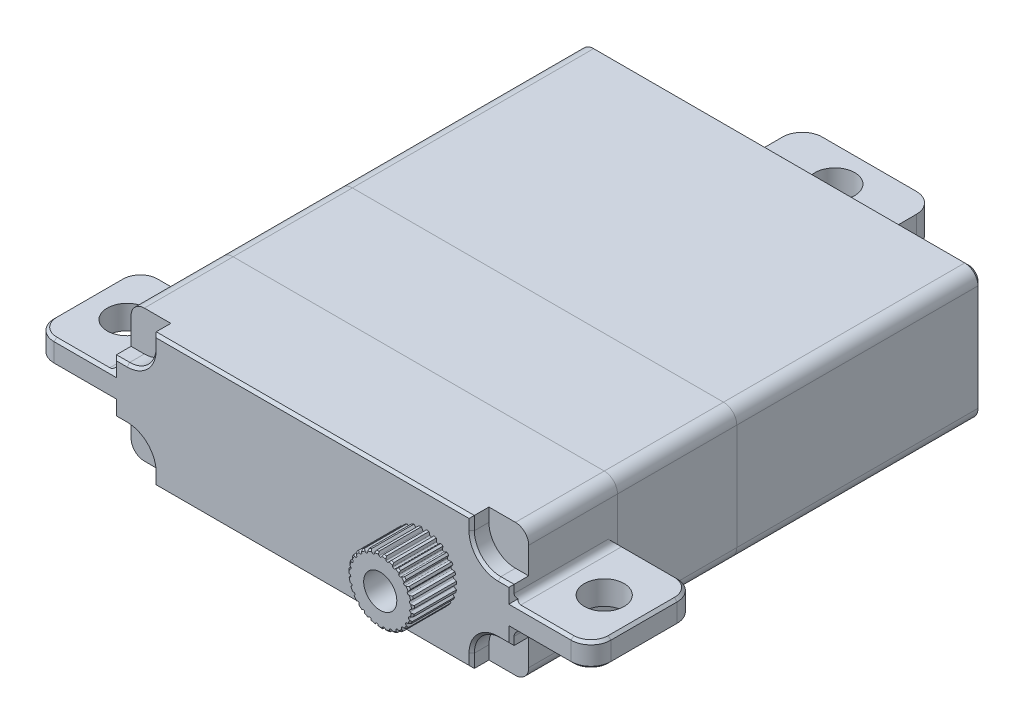
SolidWorks part; units mm, degrees
ref_plane "Front Plane" through (0, 0, 0) normal (0, 0, 1) x (1, 0, 0)
ref_plane "Top Plane" through (0, 0, 0) normal (0, 1, 0) x (1, 0, 0)
ref_plane "Right Plane" through (0, 0, 0) normal (1, 0, 0) x (0, 0, -1)
sketch "Sketch1" plane through (0, 0, 0) normal (0, 1, 0) x (1, 0, 0)
  line L1 (-15, 17.75) -> (15, 17.75)
  line L2 (-15, 17.75) -> (-15, -17.75)
  line L3 (-15, -17.75) -> (15, -17.75)
  line L4 (15, 17.75) -> (15, -17.75)
  line L5 (-15, 17.75) -> (15, -17.75) construction
  line L6 (-15, -17.75) -> (15, 17.75) construction
  point P0 (0, 0)
  dimension "D1" = 35.5
  dimension "D2" = 30
extrude "Boss-Extrude1" add sketch "Sketch1" along normal blind 10
sketch "Sketch2" plane through (0, 0, -17.75) normal (0, 0, -1) x (-1, 0, 0)
  line L1 (-5.05, 6.05) -> (5.05, 6.05)
  line L2 (-5.05, 6.05) -> (-5.05, 3.95)
  line L3 (-5.05, 3.95) -> (5.05, 3.95)
  line L4 (5.05, 6.05) -> (5.05, 3.95)
  line L5 (-5.05, 6.05) -> (5.05, 3.95) construction
  line L6 (-5.05, 3.95) -> (5.05, 6.05) construction
  point P0 (0, 5)
  dimension "D1" = 5
  dimension "D2" = 10.1
  dimension "D3" = 2.1
extrude "Boss-Extrude2" add sketch "Sketch2" along normal blind 6.5
sketch "Sketch3" plane through (0, 6.05, 0) normal (0, 1, 0) x (1, 0, 0)
  line L0 (-5.05, 24.25) -> (5.05, 24.25) construction
  circle A0 centre (0, 21.65) radius 1.5
  dimension "D1" = 3
  dimension "D2" = 2.6
extrude "Cut-Extrude1" cut sketch "Sketch3" against normal blind 6.5
fillet "Fillet1" radius 1.5 2 edges at (-5.05, 5, -24.25) (5.05, 5, -24.25)
ref_plane "Plane1" through (0, 5, 0) normal (0, 1, 0) x (1, 0, 0)
sketch "Sketch4" plane through (0, 5, 0) normal (0, 1, 0) x (1, 0, 0)
  line L1 (15, -17.75) -> (15, 17.75) construction
  line L2 (0, -5.5) -> (0, 5.5) construction
  line L3 (15, -17.75) -> (15, -9.75)
  line L4 (21, -9.75) -> (21, -17.75)
  line L5 (15, -17.75) -> (21, -17.75)
  line L6 (15, -9.75) -> (21, -9.75)
  line L7 (-15, -9.75) -> (-21, -9.75)
  line L8 (-15, -17.75) -> (-21, -17.75)
  line L9 (-21, -9.75) -> (-21, -17.75)
  line L10 (-15, -17.75) -> (-15, -9.75)
  circle A0 centre (18, -13.75) radius 1.5
  circle A1 centre (-18, -13.75) radius 1.5
  dimension "D3" = 4
  dimension "D5" = 3
  dimension "D1" = 21
  dimension "D2" = 8
  dimension "D4" = 18
extrude "Boss-Extrude3" add sketch "Sketch4" along normal blind 0.9 and the other way blind 0.9
fillet "Fillet2" radius 1.5 4 edges at (-21, 5, 9.75) (-21, 5, 17.75) (21, 5, 17.75) (21, 5, 9.75)
sketch "Sketch5" plane through (0, 0, 17.75) normal (0, 0, 1) x (1, 0, 0)
  line L0 (15, 10) -> (15, 5.9) construction
  circle A0 centre (8.4, 5) radius 2.125
  dimension "D1" = 4.25
  dimension "D2" = 5
  dimension "D3" = 6.6
extrude "Boss-Extrude4" add sketch "Sketch5" along normal blind 3.3
sketch "Sketch6" plane through (0, 0, 21.05) normal (0, 0, 1) x (1, 0, 0)
  line L0 (8.4, 10.2634) -> (8.4, -0.8448) construction
  line L1 (8.4866, 7.275) -> (8.5947, 7.4623)
  line L2 (8.3134, 7.275) -> (8.2053, 7.4623)
  line L3 (8.8404, 7.2336) -> (8.7784, 7.4409)
  line L4 (9.0089, 7.1937) -> (9.1573, 7.351)
  line L5 (9.3436, 7.0719) -> (9.3311, 7.2878)
  line L6 (9.4984, 6.9941) -> (9.6791, 7.113)
  line L7 (9.796, 6.7984) -> (9.8336, 7.0114)
  line L8 (9.9287, 6.6871) -> (10.1319, 6.7611)
  line L9 (10.1731, 6.428) -> (10.2588, 6.6266)
  line L10 (10.2765, 6.2891) -> (10.4914, 6.3142)
  line L11 (10.4546, 5.9806) -> (10.5838, 6.1541)
  line L12 (10.5232, 5.8216) -> (10.7381, 5.7965)
  line L13 (10.6254, 5.4803) -> (10.7911, 5.6194)
  line L14 (10.6555, 5.3098) -> (10.8587, 5.2358)
  line L15 (10.6762, 4.9542) -> (10.8695, 5.0512)
  line L16 (10.6661, 4.7813) -> (10.8468, 4.6624)
  line L17 (10.6043, 4.4305) -> (10.8147, 4.4804)
  line L18 (10.5546, 4.2646) -> (10.703, 4.1072)
  line L19 (10.4135, 3.9375) -> (10.6298, 3.9375)
  line L20 (10.3269, 3.7875) -> (10.4351, 3.6002)
  line L21 (10.1142, 3.5018) -> (10.3247, 3.4519)
  line L22 (9.9953, 3.3758) -> (10.0574, 3.1686)
  line L23 (9.7225, 3.1469) -> (9.9158, 3.0498)
  line L24 (9.5778, 3.0517) -> (9.5904, 2.8358)
  line L25 (9.2595, 2.8918) -> (9.4252, 2.7528)
  line L26 (9.0967, 2.8326) -> (9.0592, 2.6196)
  line L27 (8.7501, 2.7504) -> (8.8793, 2.5769)
  line L28 (8.5781, 2.7303) -> (8.4924, 2.5317)
  line L29 (8.2219, 2.7303) -> (8.3076, 2.5317)
  line L30 (8.0499, 2.7504) -> (7.9207, 2.5769)
  line L31 (7.7033, 2.8326) -> (7.7408, 2.6196)
  line L32 (7.5405, 2.8918) -> (7.3748, 2.7528)
  line L33 (7.2222, 3.0517) -> (7.2096, 2.8358)
  line L34 (7.0775, 3.1469) -> (6.8842, 3.0498)
  line L35 (6.8047, 3.3758) -> (6.7426, 3.1686)
  line L36 (6.6858, 3.5018) -> (6.4753, 3.4519)
  line L37 (6.4731, 3.7875) -> (6.3649, 3.6002)
  line L38 (6.3865, 3.9375) -> (6.1702, 3.9375)
  line L39 (6.2454, 4.2646) -> (6.097, 4.1072)
  line L40 (6.1957, 4.4305) -> (5.9853, 4.4804)
  line L41 (6.1339, 4.7813) -> (5.9532, 4.6624)
  line L42 (6.1238, 4.9542) -> (5.9305, 5.0512)
  line L43 (6.1445, 5.3098) -> (5.9413, 5.2358)
  line L44 (6.1746, 5.4803) -> (6.0089, 5.6194)
  line L45 (6.2768, 5.8216) -> (6.0619, 5.7965)
  line L46 (6.3454, 5.9806) -> (6.2162, 6.1541)
  line L47 (6.5235, 6.2891) -> (6.3086, 6.3142)
  line L48 (6.6269, 6.428) -> (6.5412, 6.6266)
  line L49 (6.8713, 6.6871) -> (6.6681, 6.7611)
  line L50 (7.004, 6.7984) -> (6.9664, 7.0114)
  line L51 (7.3016, 6.9941) -> (7.1209, 7.113)
  line L52 (7.4564, 7.0719) -> (7.4689, 7.2878)
  line L53 (7.7911, 7.1937) -> (7.6427, 7.351)
  line L54 (7.9596, 7.2336) -> (8.0216, 7.4409)
  circle A0 centre (8.4, 5) radius 2.125 construction
  circle A1 centre (8.4, 5) radius 2.125
  arc A2 (8.7784, 7.4409) -> (8.5947, 7.4623) centre (8.4, 5) ccw
  arc A3 (8.4866, 7.275) -> (8.3134, 7.275) centre (8.4, 7.325) cw
  arc A4 (9.0089, 7.1937) -> (8.8404, 7.2336) centre (8.9362, 7.2623) cw
  arc A5 (9.4984, 6.9941) -> (9.3436, 7.0719) centre (9.4435, 7.0777) cw
  arc A6 (9.9287, 6.6871) -> (9.796, 6.7984) centre (9.8945, 6.7811) cw
  arc A7 (10.2765, 6.2891) -> (10.1731, 6.428) centre (10.2649, 6.3884) cw
  arc A8 (10.5232, 5.8216) -> (10.4546, 5.9806) centre (10.5349, 5.9209) cw
  arc A9 (10.6555, 5.3098) -> (10.6254, 5.4803) centre (10.6897, 5.4037) cw
  arc A10 (10.6661, 4.7813) -> (10.6762, 4.9542) centre (10.7211, 4.8648) cw
  arc A11 (10.5546, 4.2646) -> (10.6043, 4.4305) centre (10.6273, 4.3332) cw
  arc A12 (10.3269, 3.7875) -> (10.4135, 3.9375) centre (10.4135, 3.8375) cw
  arc A13 (9.9953, 3.3758) -> (10.1142, 3.5018) centre (10.0911, 3.4045) cw
  arc A14 (9.5778, 3.0517) -> (9.7225, 3.1469) centre (9.6776, 3.0575) cw
  arc A15 (9.0967, 2.8326) -> (9.2595, 2.8918) centre (9.1952, 2.8152) cw
  arc A16 (8.5781, 2.7303) -> (8.7501, 2.7504) centre (8.6699, 2.6907) cw
  arc A17 (8.0499, 2.7504) -> (8.2219, 2.7303) centre (8.1301, 2.6907) cw
  arc A18 (7.5405, 2.8918) -> (7.7033, 2.8326) centre (7.6048, 2.8152) cw
  arc A19 (7.0775, 3.1469) -> (7.2222, 3.0517) centre (7.1224, 3.0575) cw
  arc A20 (6.6858, 3.5018) -> (6.8047, 3.3758) centre (6.7089, 3.4045) cw
  arc A21 (6.3865, 3.9375) -> (6.4731, 3.7875) centre (6.3865, 3.8375) cw
  arc A22 (6.1957, 4.4305) -> (6.2454, 4.2646) centre (6.1727, 4.3332) cw
  arc A23 (6.1238, 4.9542) -> (6.1339, 4.7813) centre (6.0789, 4.8648) cw
  arc A24 (6.1746, 5.4803) -> (6.1445, 5.3098) centre (6.1103, 5.4037) cw
  arc A25 (6.3454, 5.9806) -> (6.2768, 5.8216) centre (6.2651, 5.9209) cw
  arc A26 (6.6269, 6.428) -> (6.5235, 6.2891) centre (6.5351, 6.3884) cw
  arc A27 (7.004, 6.7984) -> (6.8713, 6.6871) centre (6.9055, 6.7811) cw
  arc A28 (7.4564, 7.0719) -> (7.3016, 6.9941) centre (7.3565, 7.0777) cw
  arc A29 (7.9596, 7.2336) -> (7.7911, 7.1937) centre (7.8638, 7.2623) cw
  arc A30 (9.3311, 7.2878) -> (9.1573, 7.351) centre (8.4, 5) ccw
  arc A31 (9.8336, 7.0114) -> (9.6791, 7.113) centre (8.4, 5) ccw
  arc A32 (10.2588, 6.6266) -> (10.1319, 6.7611) centre (8.4, 5) ccw
  arc A33 (10.5838, 6.1541) -> (10.4914, 6.3142) centre (8.4, 5) ccw
  arc A34 (10.7911, 5.6194) -> (10.7381, 5.7965) centre (8.4, 5) ccw
  arc A35 (10.8695, 5.0512) -> (10.8587, 5.2358) centre (8.4, 5) ccw
  arc A36 (10.8147, 4.4804) -> (10.8468, 4.6624) centre (8.4, 5) ccw
  arc A37 (10.6298, 3.9375) -> (10.703, 4.1072) centre (8.4, 5) ccw
  arc A38 (10.3247, 3.4519) -> (10.4351, 3.6002) centre (8.4, 5) ccw
  arc A39 (9.9158, 3.0498) -> (10.0574, 3.1686) centre (8.4, 5) ccw
  arc A40 (9.4252, 2.7528) -> (9.5904, 2.8358) centre (8.4, 5) ccw
  arc A41 (8.8793, 2.5769) -> (9.0592, 2.6196) centre (8.4, 5) ccw
  arc A42 (8.3076, 2.5317) -> (8.4924, 2.5317) centre (8.4, 5) ccw
  arc A43 (7.7408, 2.6196) -> (7.9207, 2.5769) centre (8.4, 5) ccw
  arc A44 (7.2096, 2.8358) -> (7.3748, 2.7528) centre (8.4, 5) ccw
  arc A45 (6.7426, 3.1686) -> (6.8842, 3.0498) centre (8.4, 5) ccw
  arc A46 (6.3649, 3.6002) -> (6.4753, 3.4519) centre (8.4, 5) ccw
  arc A47 (6.097, 4.1072) -> (6.1702, 3.9375) centre (8.4, 5) ccw
  arc A48 (5.9532, 4.6624) -> (5.9853, 4.4804) centre (8.4, 5) ccw
  arc A49 (5.9413, 5.2358) -> (5.9305, 5.0512) centre (8.4, 5) ccw
  arc A50 (6.0619, 5.7965) -> (6.0089, 5.6194) centre (8.4, 5) ccw
  arc A51 (6.3086, 6.3142) -> (6.2162, 6.1541) centre (8.4, 5) ccw
  arc A52 (6.6681, 6.7611) -> (6.5412, 6.6266) centre (8.4, 5) ccw
  arc A53 (7.1209, 7.113) -> (6.9664, 7.0114) centre (8.4, 5) ccw
  arc A54 (7.6427, 7.351) -> (7.4689, 7.2878) centre (8.4, 5) ccw
  arc A55 (8.2053, 7.4623) -> (8.0216, 7.4409) centre (8.4, 5) ccw
  point P11 (8.4, 7.125)
  point P12 (0, 0)
  point P13 (0, 0)
  point P144 (8.4, 5)
  dimension "D1" = 4.94
  dimension "D3" = 0.1
  dimension "D2" = 30
  dimension "D4" = 27
extrude "Boss-Extrude5" add sketch "Sketch6" against normal blind 3.3
sketch "Sketch7" plane through (0, 0, 21.05) normal (0, 0, 1) x (1, 0, 0)
  circle A0 centre (8.4, 5) radius 1.25
  circle A1 centre (8.4, 5) radius 2.125
  circle A2 centre (8.4, 5) radius 2.125 construction
  dimension "D2" = 2.5
  dimension "D1" = 0
extrude "Cut-Extrude2" cut sketch "Sketch7" against normal blind 3.3 contours A0
sketch "Sketch8" plane through (0, 5, 0) normal (0, 1, 0) x (1, 0, 0)
  line L0 (10.6364, -21.1399) -> (10.9206, -20.9038)
  line L1 (10.9206, -20.9038) -> (10.9206, -21.1399)
  line L2 (10.9206, -21.1399) -> (10.6364, -21.1399)
  point P2 (10.9206, -20.9809)
sketch "Sketch9" plane through (0, 5, 0) normal (0, 1, 0) x (1, 0, 0)
  line L0 (7.15, -21.05) -> (9.65, -21.05) construction
  line L1 (7.15, -21.05) -> (9.65, -21.05) construction
  line L2 (8.4, -21.05) -> (8.4, -14.4103) construction
revolve "Cut-Revolve1" cut sketch "Sketch8" angle 360 about L2
sketch "Sketch10" plane through (0, 0, 17.75) normal (0, 0, 1) x (1, 0, 0)
  line L0 (15, 10) -> (15, 5.9) construction
  line L1 (-15, 10) -> (15, 10) construction
  line L2 (15, 10) -> (15, 7)
  line L3 (12, 10) -> (15, 10)
  line L4 (12, 10) -> (12, 9)
  line L5 (14, 7) -> (15, 7)
  line L6 (0, -5.5) -> (0, 5.5) construction
  line L7 (-14, 7) -> (-15, 7)
  line L8 (-12, 10) -> (-12, 9)
  line L9 (-12, 10) -> (-15, 10)
  line L10 (-15, 10) -> (-15, 7)
  line L11 (23.1, 5) -> (-23.1, 5) construction
  line L12 (-15, 0) -> (-15, 3)
  line L13 (-12, 0) -> (-15, 0)
  line L14 (-12, 0) -> (-12, 1)
  line L15 (-14, 3) -> (-15, 3)
  line L16 (14, 3) -> (15, 3)
  line L17 (12, 0) -> (12, 1)
  line L18 (12, 0) -> (15, 0)
  line L19 (15, 0) -> (15, 3)
  arc A0 (14, 7) -> (12, 9) centre (14, 9) cw
  arc A1 (-14, 7) -> (-12, 9) centre (-14, 9) ccw
  arc A2 (-14, 3) -> (-12, 1) centre (-14, 1) cw
  arc A3 (14, 3) -> (12, 1) centre (14, 1) ccw
  dimension "D3" = 2
  dimension "D1" = 3
  dimension "D2" = 3
extrude "Cut-Extrude3" cut sketch "Sketch10" against normal blind 1.3
fillet "Fillet3" radius 1 4 edges at (15, 10, -0.65) (-15, 10, -0.65) (15, 0, -0.65) (-15, 0, -0.65)
chamfer "Chamfer1" distance 0.3 angle 45 8 edges at (-14.7071, 0.2929, -17.75) (-15, 5, -17.75) (-14.7071, 9.7071, -17.75) (0, 10, -17.75) (14.7071, 9.7071, -17.75) (15, 5, -17.75) (14.7071, 0.2929, -17.75) (0, 0, -17.75)
chamfer "Chamfer2" distance 0.2 angle 45 38 edges at (-17.25, 5.9, 9.75) (17.25, 5.9, 9.75) (-20.5607, 5.9, 10.1893) (20.5607, 5.9, 10.1893) (-21, 5.9, 13.75) (21, 5.9, 13.75) (-20.5607, 5.9, 17.3107) (20.5607, 5.9, 17.3107) (-17.25, 5.9, 17.75) (-15, 6.45, 17.75) (-14.5, 7, 17.75) (-12.5858, 7.5858, 17.75) (-12, 9.5, 17.75) (0, 10, 17.75) (12, 9.5, 17.75) (12.5858, 7.5858, 17.75) (14.5, 7, 17.75) (15, 6.45, 17.75) (17.25, 5.9, 17.75) (-17.25, 4.1, 9.75) (17.25, 4.1, 9.75) (-20.5607, 4.1, 10.1893) (20.5607, 4.1, 10.1893) (-21, 4.1, 13.75) (21, 4.1, 13.75) (-20.5607, 4.1, 17.3107) (20.5607, 4.1, 17.3107) (-17.25, 4.1, 17.75) (-15, 3.55, 17.75) (-14.5, 3, 17.75) (-12.5858, 2.4142, 17.75) (-12, 0.5, 17.75) (0, 0, 17.75) (12, 0.5, 17.75) (17.25, 4.1, 17.75) (15, 3.55, 17.75) (14.5, 3, 17.75) (12.5858, 2.4142, 17.75)
fillet "Fillet4" radius 0.5 4 edges at (-15, 4.1, 13.75) (-15, 5.9, 13.75) (15, 5.9, 13.75) (15, 4.1, 13.75)
sketch "Sketch11" plane through (0, 5, 0) normal (0, 1, 0) x (1, 0, 0)
  line L0 (15, -9.75) -> (19.5, -9.75) construction
  line L1 (15, -9.75) -> (18.2907, -9.75)
  line L2 (15, -9.75) -> (-16.1873, -9.75)
  line L3 (-19.5, -9.75) -> (-15, -9.75) construction
  line L4 (-16.1873, -9.75) -> (-16.1873, -0.75)
  line L5 (-16.1873, -0.75) -> (18.2907, -0.75)
  line L6 (18.2907, -0.75) -> (18.2907, -9.75)
  dimension "D1" = 9
split line "Split Line1"
sketch "Sketch12" plane through (0, 0, 0) normal (0, -1, 0) x (1, 0, 0)
  text T0 "KST" font "@Adobe Gothic Std B" height 3
  point P1 (0, 0)
split line "Split Line2"
curve "Curve1"
sketch "Sketch12<2>" plane through (0, 0, 0) normal (0, -1, 0) x (1, 0, 0) same geometry as "Sketch12"
